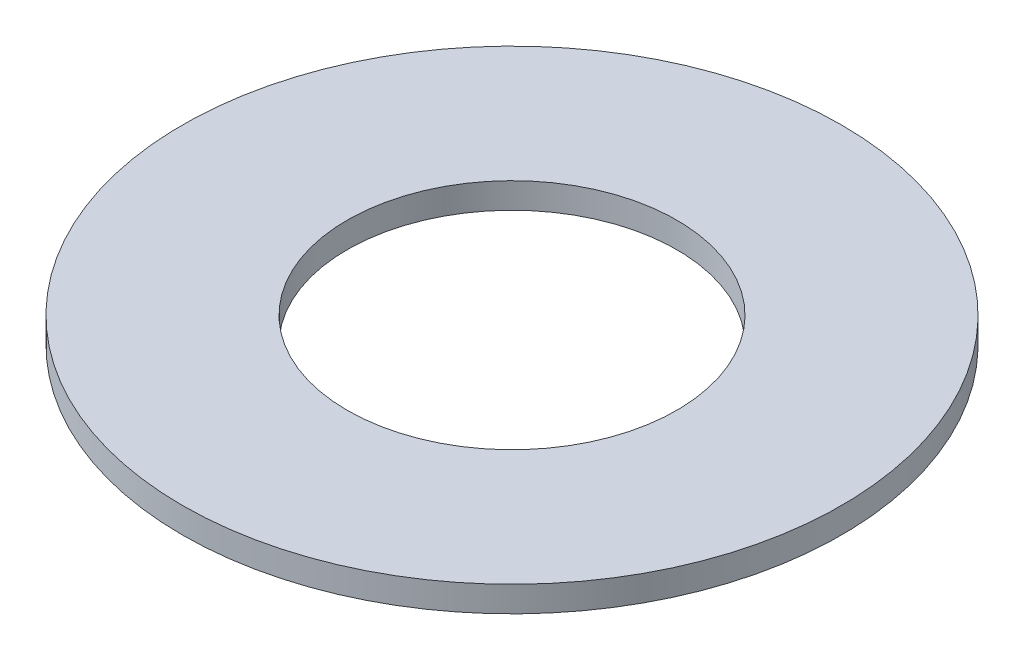
SolidWorks part; units mm, degrees
ref_plane "Front Plane" through (0, 0, 0) normal (0, 0, 1) x (1, 0, 0)
ref_plane "Top Plane" through (0, 0, 0) normal (0, 1, 0) x (1, 0, 0)
ref_plane "Right Plane" through (0, 0, 0) normal (1, 0, 0) x (0, 0, -1)
sketch "Sketch1" plane through (0, 0, 0) normal (0, 1, 0) x (1, 0, 0)
  circle A0 centre (0, 0) radius 90
  dimension "FLANGE_OD" = 180
extrude "Boss-Extrude1" add sketch "Sketch1" along normal blind 7
sketch "Sketch2" plane through (0, 0, 0) normal (0, 1, 0) x (1, 0, 0)
  circle A0 centre (0, 0) radius 45
  dimension "BORE_D" = 90
extrude "Cut-Extrude1" cut sketch "Sketch2" along normal through all
sketch "Sketch3" plane through (0, 7, 0) normal (0, 1, 0) x (1, 0, 0)
  circle A0 centre (0, 0) radius 31.0535 construction
  circle A1 centre (-31.0535, 0) radius 7.5268
  dimension "BOLT_D" = 15.0535
  dimension "BOLT_PCD" = 62.107
extrude "Cut-Extrude2" cut sketch "Sketch3" against normal blind 6.2126 rebuild error yes
pattern_circular "CirPattern1" count 5 over 360 rebuild error yes
